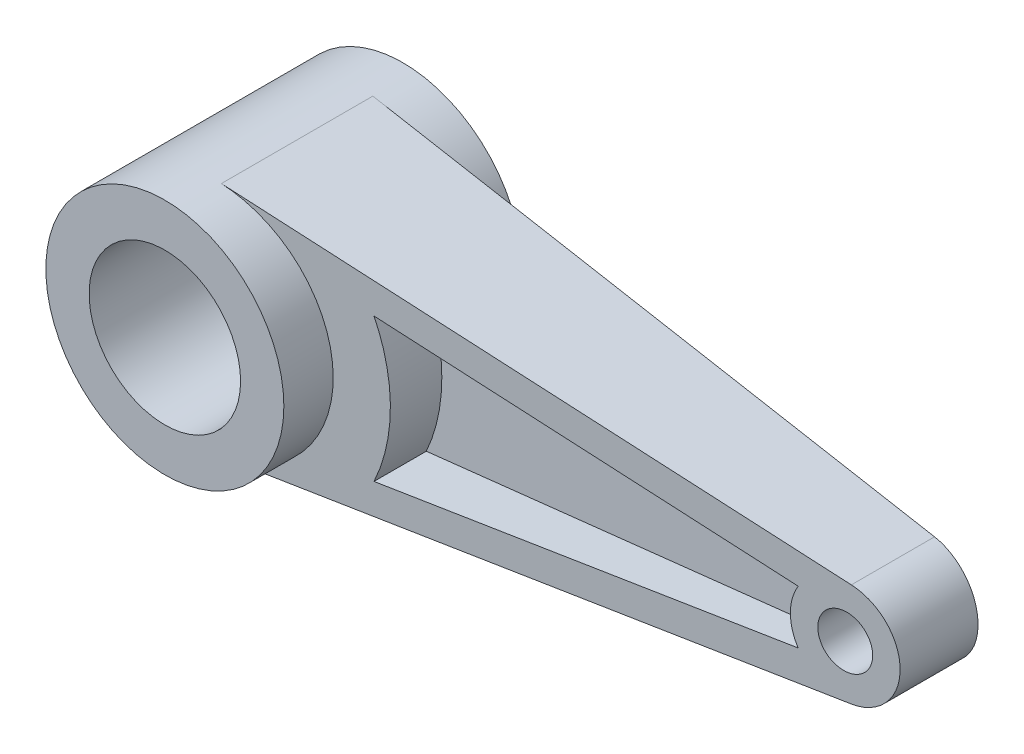
SolidWorks part; units mm, degrees
ref_plane "Front Plane" through (0, 0, 0) normal (0, 0, 1) x (1, 0, 0)
ref_plane "Top Plane" through (0, 0, 0) normal (0, 1, 0) x (1, 0, 0)
ref_plane "Right Plane" through (0, 0, 0) normal (1, 0, 0) x (0, 0, -1)
sketch "Sketch1" plane through (0, 0, 0) normal (0, 0, 1) x (1, 0, 0)
  line L0 (3.0577, 27.3295) -> (140.735, 11.9256)
  line L1 (3.0577, -27.3295) -> (140.735, -11.9256)
  circle A0 centre (0, 0) radius 27.5
  circle A1 centre (139.4007, 0) radius 12
  dimension "D1" = 55
extrude "Boss-Extrude1" add sketch "Sketch1" along normal mid plane 55 contours A0 region at (0, 0, 0)
extrude "Boss-Extrude2" add sketch "Sketch1<3>" along normal mid plane 35 contours A1 L0 A0 L1 | A1 region at (70.6296, 0, 0) region at (139.4007, 0, 0)
sketch "Sketch1<3>" plane through (0, 0, 0) normal (0, 0, 1) x (1, 0, 0) same geometry as "Sketch1"
sketch "Sketch2" plane through (0, 0, 0) normal (0, 1, 0) x (1, 0, 0)
  line L0 (151.4007, -9) -> (151.4007, 9)
  line L1 (151.4007, -17.5) -> (151.4007, 17.5) construction
  line L2 (3.0577, -17.5) -> (151.4007, -9)
  line L3 (151.4007, -17.5) -> (3.0577, -17.5)
  line L4 (151.4007, 9) -> (151.4007, 17.5)
  line L5 (151.4007, 17.5) -> (3.0577, 17.5)
  line L6 (3.0577, 17.5) -> (151.4007, 9)
  line L7 (151.4007, -9) -> (151.4007, -17.5)
  point P4 (151.4007, 0)
extrude "Cut-Extrude1" cut sketch "Sketch2" against normal mid plane 68 contours L5 L6 L4 | L7 L2 L3 region at (101.953, 0, -14.6667) region at (101.953, 0, 14.6667)
sketch "Sketch3" plane through (0, 0, 0) normal (0, 0, 1) x (1, 0, 0)
  circle A0 centre (0, 0) radius 17.5
  circle A1 centre (139.4007, 0) radius 6
  dimension "D1" = 35
  dimension "D2" = 12
extrude "Cut-Extrude2" cut sketch "Sketch3" against normal mid plane 68
ref_plane "Plane1" through (0, 0, 3.5) normal (0, 0, 1) x (1, 0, 0)
sketch "Sketch7" plane through (0, 0, 3.5) normal (0, 0, 1) x (1, 0, 0)
  line L0 (36.4139, 16.5538) -> (129.1156, 6.1819)
  line L1 (36.4139, -16.5538) -> (129.1156, -6.1819)
  arc A0 (36.4139, -16.5538) -> (36.4139, 16.5538) centre (0, 0) ccw
  arc A1 (129.1156, 6.1819) -> (129.1156, -6.1819) centre (139.4007, 0) ccw
extrude "Cut-Extrude6" cut sketch "Sketch7" along normal blind 53
mirror "Mirror2" about plane through (0, 0, 0) normal (0, 0, 1) of "Cut-Extrude6"
sketch "Sketch8" plane through (0, 0, 0) normal (0, 0, 1) x (1, 0, 0)
  circle A0 centre (0, 0) radius 27.5
extrude "Cut-Extrude7" cut sketch "Sketch8" against normal mid plane 94
sketch "Sketch9" plane through (0, 0, 0) normal (0, 0, 1) x (1, 0, 0)
  circle A0 centre (0, 0) radius 27.5
  circle A1 centre (0, 0) radius 17.5
  dimension "D1" = 35
extrude "Boss-Extrude3" add sketch "Sketch9" along normal mid plane 55
